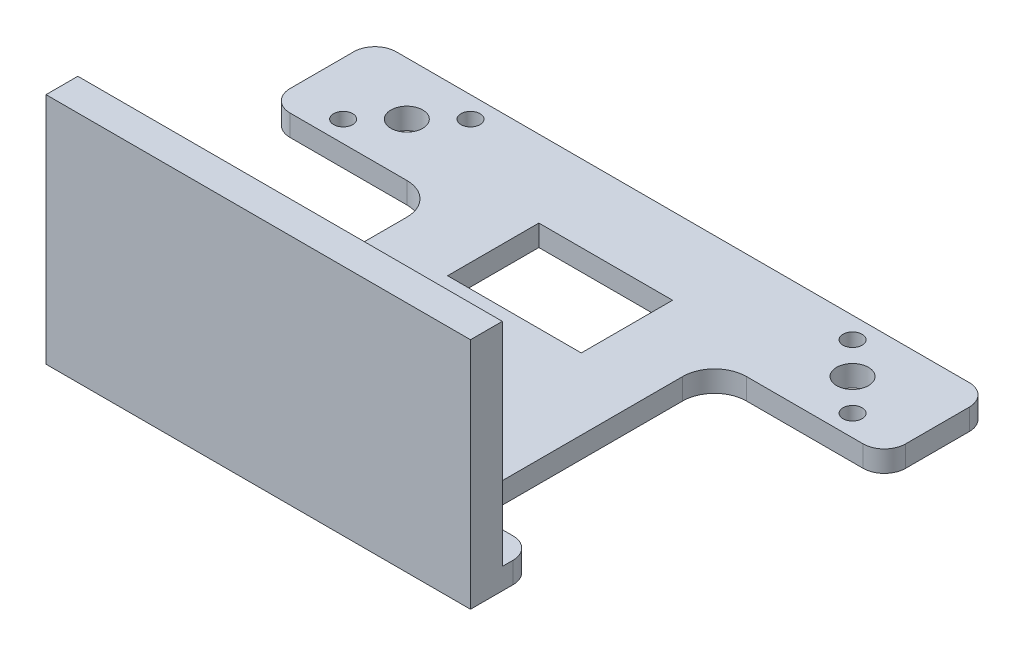
SolidWorks part; units mm, degrees
ref_plane "Vorne" through (0, 0, 0) normal (0, 0, 1) x (1, 0, 0)
ref_plane "Oben" through (0, 0, 0) normal (0, 1, 0) x (1, 0, 0)
ref_plane "Rechts" through (0, 0, 0) normal (1, 0, 0) x (0, 0, -1)
ref_plane "E_Boden" through (0, 1, 0) normal (0, 1, 0) x (1, 0, 0)
sketch "Skizze1" plane through (0, 0, 0) normal (0, 1, 0) x (1, 0, 0)
  line L0 (0, -133.037) -> (0, 127.1868) construction
  line L1 (-165.4867, 0) -> (188.3198, 0) construction
  line L2 (-135, 100) -> (135, 100)
  line L3 (-145, 90) -> (-145, 60)
  line L8 (-135, 50) -> (-80, 50)
  line L9 (-65, 35) -> (-65, -55)
  line L10 (-80, -70) -> (-90, -70)
  line L11 (-100, -80) -> (-100, -90)
  line L12 (-90, -100) -> (90, -100)
  line L13 (100, -80) -> (100, -90)
  line L14 (80, -70) -> (90, -70)
  line L15 (65, 35) -> (65, -55)
  line L16 (135, 50) -> (80, 50)
  line L17 (145, 90) -> (145, 60)
  line L18 (0, 75) -> (-156.9097, 75) construction
  line L19 (0, 90) -> (-140.2601, 90) construction
  line L20 (0, 60) -> (-133.7021, 60) construction
  line L21 (-120, 60) -> (-120, 109.8946) construction
  line L22 (-90, 90) -> (-90, 110.5565) construction
  line L23 (-105, 75) -> (-105, 35) construction
  line L24 (-105, 35) -> (-105, 140.5126) construction
  line L25 (-31.5, 63.715) -> (31.5, 63.715)
  line L26 (31.5, 63.715) -> (31.5, 20.705)
  line L27 (31.5, 20.705) -> (-31.5, 20.705)
  line L28 (-31.5, 20.705) -> (-31.5, 63.715)
  line L29 (0, 42.21) -> (-56.3168, 42.21) construction
  line L30 (-56.3168, 42.21) -> (55.721, 42.21) construction
  line L31 (-100, -90) -> (-100, -100)
  line L32 (-100, -100) -> (-90, -100)
  line L33 (90, -100) -> (100, -100)
  line L34 (100, -100) -> (100, -90)
  arc A0 (65, 35) -> (80, 50) centre (80, 35) cw
  arc A1 (80, -70) -> (65, -55) centre (80, -55) cw
  arc A2 (-65, -55) -> (-80, -70) centre (-80, -55) cw
  arc A3 (-80, 50) -> (-65, 35) centre (-80, 35) cw
  arc A4 (100, -80) -> (90, -70) centre (90, -80) ccw
  arc A7 (-90, -70) -> (-100, -80) centre (-90, -80) ccw
  arc A8 (-145, 60) -> (-135, 50) centre (-135, 60) ccw
  arc A9 (135, 50) -> (145, 60) centre (135, 60) ccw
  arc A10 (145, 90) -> (135, 100) centre (135, 90) ccw
  arc A11 (-135, 100) -> (-145, 90) centre (-135, 90) ccw
  circle A12 centre (-105, 75) radius 7.5
  circle A13 centre (105, 75) radius 7.5
  circle A14 centre (-90, 90) radius 4.5
  circle A15 centre (-120, 60) radius 4.5
  circle A16 centre (90, 90) radius 4.5
  circle A17 centre (120, 60) radius 4.5
  point P15 (0, -100)
  point P16 (0, 100)
  point P22 (65, 50)
  point P25 (65, -70)
  point P28 (-65, -70)
  point P31 (-65, 50)
  point P34 (100, -70)
  point P37 (100, -100)
  point P40 (-100, -100)
  point P43 (-100, -70)
  point P46 (-145, 50)
  point P49 (145, 50)
  point P52 (145, 100)
  point P55 (-145, 100)
  point P77 (0, 42.21)
  dimension "D7" = 15
  dimension "D8" = 10
  dimension "D9" = 15
  dimension "D13" = 9
  dimension "D14" = 9
  dimension "D20" = 10
  dimension "D1" = 290
  dimension "D2" = 50
  dimension "D3" = 150
  dimension "D4" = 200
  dimension "D5" = 130
  dimension "D6" = 30
  dimension "D10" = 210
  dimension "D11" = 30
  dimension "D12" = 15
  dimension "D15" = 30
  dimension "D16" = 15
  dimension "D17" = 32.79
  dimension "D18" = 63
  dimension "D19" = 43.01
extrude "Aufsatz-Linear austragen1" add sketch "Skizze1" along normal blind 10
sketch "Skizze2" plane through (0, 10, 0) normal (0, 1, 0) x (1, 0, 0)
sketch "Skizze3" plane through (0, 10, 0) normal (0, 1, 0) x (1, 0, 0)
  line L0 (-100, -80) -> (-100, -100) construction
  line L1 (-100, -85) -> (100, -85)
  line L2 (-100, -85) -> (-100, -100)
  line L3 (-100, -100) -> (100, -100)
  line L4 (100, -85) -> (100, -100)
  dimension "D1" = 15
extrude "Aufsatz-Linear austragen2" add sketch "Skizze3" along normal blind 100
sketch "Skizze7" plane through (0, 0, 0) normal (1, 0, 0) x (0, 0, -1)
  line L0 (-85, 70.7062) -> (-15, 10)
  line L1 (-85, 110) -> (-85, 10) construction
  line L2 (35, 10) -> (-55, 10) construction
  dimension "D1" = 70
rib "Verstärkungsrippe1" sketch "Skizze7" sketch "Skizze7" thickness 10 extrusion direction parallel to sketch draft on no parameters "D1"=10
